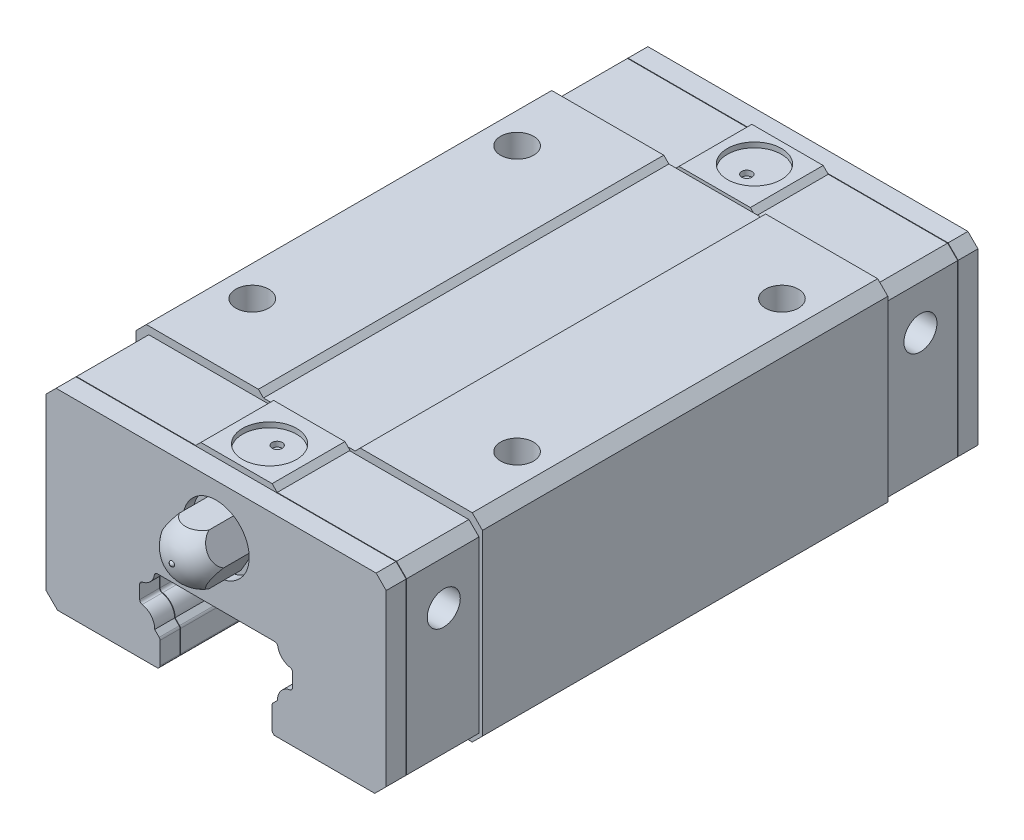
SolidWorks part; units mm, degrees
ref_plane "Front Plane" through (0, 0, 0) normal (0, 0, 1) x (1, 0, 0)
ref_plane "Top Plane" through (0, 0, 0) normal (0, 1, 0) x (1, 0, 0)
ref_plane "Right Plane" through (0, 0, 0) normal (1, 0, 0) x (0, 0, -1)
ref_axis "Axis_X" through (-18.7, 0, 0) along (1, 0, 0)
ref_axis "Axis_Y" through (0, 12.475, 0) along (0, -1, 0)
ref_axis "Axis_Z" through (0, 0, -62.49) along (0, 0, 1)
sketch "Sketch1" plane through (0, 0, 0) normal (0, 0, 1) x (1, 0, 0)
  line L0 (0, 0) -> (0, -12.5) construction
  line L1 (-17, -8) -> (-5.7, -8) construction
  line L2 (-17, -8) -> (-17, 11.5) construction
  line L3 (-17, 11.5) -> (17, 11.5) construction
  line L4 (17, -8) -> (17, 11.5) construction
  line L5 (-17, -8) -> (17, 11.5) construction
  line L6 (-17, 11.5) -> (17, -8) construction
  line L7 (-5.7, -8) -> (-5.5, -7.8)
  line L8 (-5.5, -7.8) -> (-5.5, -5.4)
  line L9 (-5.5, -5.4) -> (-7.5, -5.4)
  line L10 (-7.5, -5.4) -> (-7.5, 0)
  line L11 (7.5, -5.4) -> (7.5, 0)
  line L12 (-7.5, 0) -> (7.5, 0)
  line L13 (5.5, -5.4) -> (7.5, -5.4)
  line L14 (5.5, -7.8) -> (5.5, -5.4)
  line L15 (5.7, -8) -> (5.5, -7.8)
  line L16 (5.7, -8) -> (17, -8) construction
  line L17 (-17, -7) -> (-16, -8)
  line L18 (16, -8) -> (17, -7)
  line L19 (-16, -8) -> (-5.7, -8)
  line L20 (-17, 10.5) -> (-17, -7)
  line L21 (5.7, -8) -> (16, -8)
  line L22 (-16, 11.5) -> (16, 11.5)
  line L23 (-17, 10.5) -> (-16, 11.5)
  line L24 (16, 11.5) -> (17, 10.5)
  line L25 (17, 10.5) -> (17, -7)
  point P0 (0, 1.75)
  dimension "W" = 34
  dimension "HR" = 12.5
  dimension "H" = 24
  dimension "H1" = 4.5
  dimension "MSM_21" = 11.4
  dimension "FIX_1" = 45
  dimension "MSM_1" = 11
  dimension "MSM_4" = 7.1
  dimension "WR" = 15
  dimension "FIX_2" = 45
  dimension "FIX_3" = 1
extrude "Boss-Extrude1" add sketch "Sketch1" against normal blind 58.1
sketch "Sketch2" plane through (0, 0, 0) normal (0, 0, 1) x (1, 0, 0)
  line L0 (0, 0) -> (0, 11.5) construction
  line L1 (-7.5, 0) -> (7.5, 0) construction
  line L2 (16, 11.5) -> (-16, 11.5) construction
  line L3 (-5.5, -5.4) -> (-6.0305, -4.8695)
  line L4 (-5.7, -8) -> (-5.5, -7.8) construction
  line L5 (5.5, -5.4) -> (6.0305, -4.8695)
  line L6 (-7.53, -6.33) -> (-5.5, -6.33)
  line L7 (-5.5, -7.8) -> (-5.5, -5.4) construction
  line L8 (-5.5, -6.33) -> (-5.5, -5.4)
  line L9 (7.53, -6.33) -> (5.5, -6.33)
  line L10 (5.5, -5.4) -> (5.5, -7.8) construction
  line L11 (5.5, -6.33) -> (5.5, -5.4)
  circle A0 centre (-7.53, 0.03) radius 1.5
  arc A1 (6.0305, -4.8695) -> (7.53, -6.33) centre (7.53, -4.83) cw
  arc A2 (-6.0305, -4.8695) -> (-7.53, -6.33) centre (-7.53, -4.83) ccw
  circle A3 centre (7.53, 0.03) radius 1.5
  dimension "MSM_5" = 3
  dimension "MSM_6" = 15.06
  dimension "MSM_7" = 4.86
  dimension "MSM_8" = 7.67
extrude "Boss-Extrude2" add sketch "Sketch2" against normal through all
fillet "Fillet1" radius 0.3 6 edges at (7.5, -3.3303, -29.05) (7.5, -1.4697, -29.05) (-7.5, -3.3303, -29.05) (-7.5, -1.4697, -29.05) (6.0303, 0, -29.05) (-6.0303, 0, -29.05)
fillet "Fillet2" radius 0.3 4 edges at (-5.5, -7.8, -29.05) (5.5, -7.8, -29.05) (5.5, -5.4, -29.05) (-5.5, -5.4, -29.05)
sketch "Sketch3" plane through (0, 0, 0) normal (0, 0, 1) x (1, 0, 0)
  line L4 (15.7101, 10.8) -> (16.7, 9.8101)
  line L7 (-15.7101, 10.8) -> (15.7101, 10.8)
  line L11 (-16, 11.5) -> (-17, 10.5)
  line L12 (-15.7101, 10.8) -> (-16.7, 9.8101)
  line L13 (-17, 10.5) -> (-17, -7)
  line L14 (-16, 11.5) -> (16, 11.5)
  line L15 (16, 11.5) -> (17, 10.5)
  line L16 (-17, -7) -> (-16, -8)
  line L17 (17, 10.5) -> (17, -7)
  line L18 (17, -7) -> (16, -8)
  line L20 (16, -8) -> (17, -7) construction
  line L21 (16.7, -6.8757) -> (15.5757, -8)
  line L22 (16.7, 9.8101) -> (16.7, -6.8757)
  line L23 (-15.7101, 10.8) -> (-16.505, 10.005) construction
  line L24 (15.7101, 10.8) -> (16.505, 10.005) construction
  line L25 (-16.7, -6.8757) -> (-15.7879, -7.7879) construction
  line L26 (-16.7, 9.8101) -> (-16.7, -6.8757)
  line L27 (-16.7, -6.8757) -> (-15.5757, -8)
  line L28 (-15.8757, 11.2) -> (-16.7, 10.3757) construction
  line L29 (-15.8757, 11.2) -> (15.8757, 11.2) construction
  line L30 (15.8757, 11.2) -> (16.7, 10.3757) construction
  line L31 (-16.7, 10.3757) -> (-16.7, -6.8757) construction
  line L32 (16.7, 10.3757) -> (16.7, -6.8757) construction
  line L33 (-16, -8) -> (-5.7, -8) construction
  line L34 (-16, -8) -> (-15.5757, -8)
  line L35 (16.7, -6.8757) -> (15.7879, -7.7879) construction
  line L36 (5.7, -8) -> (16, -8) construction
  line L37 (17, -7) -> (16, -8) construction
  line L38 (15.5757, -8) -> (16, -8)
  point P11 (-16.7, -6.8757)
  point P12 (-16.7, 11.2)
  point P13 (16.7, 11.2)
  point P14 (16.7, -6.8757)
  dimension "KSS_1" = 0.7
  dimension "FIX_5" = 0.3
extrude "Cut-Extrude1" cut sketch "Sketch3" against normal blind 9.15
ref_plane "Plane1" through (0, 0, -48.95) normal (0, 0, 1) x (1, 0, 0)
sketch "Sketch4" plane through (0, 0, -48.95) normal (0, 0, 1) x (1, 0, 0)
  line L8 (-16, -8) -> (-15.5757, -8)
  line L9 (-16, -8) -> (-15.5757, -8)
  line L10 (-16, 11.5) -> (-17, 10.5)
  line L11 (-16, 11.5) -> (-17, 10.5)
  line L12 (-16.7, 9.8101) -> (-15.7101, 10.8)
  line L13 (-16.7, 9.8101) -> (-15.7101, 10.8)
  line L14 (-15.5757, -8) -> (-16.7, -6.8757)
  line L15 (-15.5757, -8) -> (-16.7, -6.8757)
  line L16 (-16.7, -6.8757) -> (-16.7, 9.8101)
  line L17 (-16.7, -6.8757) -> (-16.7, 9.8101)
  line L18 (16, -8) -> (17, -7)
  line L19 (16, -8) -> (17, -7)
  line L20 (17, -7) -> (17, 10.5)
  line L21 (17, -7) -> (17, 10.5)
  line L22 (-17, -7) -> (-16, -8)
  line L23 (-17, -7) -> (-16, -8)
  line L28 (17, 10.5) -> (16, 11.5)
  line L29 (17, 10.5) -> (16, 11.5)
  line L30 (-15.7101, 10.8) -> (15.7101, 10.8)
  line L31 (-15.7101, 10.8) -> (15.7101, 10.8)
  line L32 (-17, 10.5) -> (-17, -7)
  line L33 (-17, 10.5) -> (-17, -7)
  line L34 (16, 11.5) -> (-16, 11.5)
  line L35 (16, 11.5) -> (-16, 11.5)
  line L40 (15.7101, 10.8) -> (16.7, 9.8101)
  line L41 (15.7101, 10.8) -> (16.7, 9.8101)
  line L42 (16.7, 9.8101) -> (16.7, -6.8757)
  line L43 (16.7, 9.8101) -> (16.7, -6.8757)
  line L44 (16.7, -6.8757) -> (15.5757, -8)
  line L45 (16.7, -6.8757) -> (15.5757, -8)
  line L46 (15.5757, -8) -> (16, -8)
  line L47 (15.5757, -8) -> (16, -8)
  dimension "FIX_6" = 0
extrude "Cut-Extrude2" cut sketch "Sketch4" against normal through all
sketch "Sketch5" plane through (0, 0, -9.15) normal (0, 0, 1) x (1, 0, 0)
  line L0 (-4.5, 11) -> (4.5, 11)
  line L1 (0, 0) -> (0, 11) construction
  line L3 (-4.5, 11) -> (-5, 11.5)
  line L4 (4.5, 11) -> (5, 11.5)
  line L5 (-5, 11.5) -> (5, 11.5)
  line L6 (16, 11.5) -> (-16, 11.5) construction
  dimension "MSM_23" = 10
  dimension "FIX_7" = 0.5
  dimension "FIX_8" = 135
extrude "Cut-Extrude3" cut sketch "Sketch5" against normal through all
sketch "Sketch6" plane through (0, 10.8, 0) normal (0, 1, 0) x (1, 0, 0)
  line L0 (0, 0) -> (0, 2) construction
  line L1 (-4, 56.1) -> (4, 56.1)
  line L2 (-4, 56.1) -> (-4, 48.95)
  line L3 (-4, 48.95) -> (4, 48.95)
  line L4 (4, 56.1) -> (4, 48.95)
  line L5 (-4, 9.15) -> (4, 9.15)
  line L6 (-4, 9.15) -> (-4, 2)
  line L7 (-4, 2) -> (4, 2)
  line L8 (4, 9.15) -> (4, 2)
  line L9 (-15.7101, 9.15) -> (15.7101, 9.15) construction
  line L10 (-4.5, 48.95) -> (4.5, 48.95) construction
  dimension "MSM_24" = 7.15
  dimension "MSM_25" = 8
extrude "Boss-Extrude3" add sketch "Sketch6" along normal blind 0.5
chamfer "Chamfer1" distance 0.5 angle 45 4 edges at (4, 11.3, -5.575) (-4, 11.3, -5.575) (4, 11.3, -52.525) (-4, 11.3, -52.525)
sketch "Sketch7" plane through (0, 0, -48.95) normal (0, 0, -1) x (-1, 0, 0)
  line L0 (5, 11.5) -> (16, 11.5) construction
  line L9 (15.5757, -8) -> (16, -8)
  line L10 (16, -8) -> (17, -7)
  line L11 (17, -7) -> (17, 5.5)
  line L12 (17, 10.5) -> (17, -7) construction
  line L15 (16.7, 5.2) -> (16.7, -6.8757)
  line L16 (16.7, -6.8757) -> (15.5757, -8)
  line L18 (17, 5.5) -> (16.7, 5.2)
  dimension "T" = 6
  dimension "FIX_10" = 45
extrude "Cut-Extrude4" cut sketch "Sketch7" against normal through all
sketch "Sketch8" plane through (0, 11.3, 0) normal (0, 1, 0) x (1, 0, 0)
  line L3 (0, 2) -> (0, 56.1) construction
  line L4 (-4, 2) -> (4, 2) construction
  line L5 (4, 56.1) -> (-4, 56.1) construction
  line L6 (-15.7101, 58.1) -> (15.7101, 58.1) construction
  circle A0 centre (0, 52.85) radius 2.65
  circle A1 centre (0, 5.25) radius 2.65
  dimension "KSS_4" = 5.3
extrude "Cut-Extrude5" cut sketch "Sketch8" against normal blind 0.5
sketch "Sketch9" plane through (0, 10.8, 0) normal (0, 1, 0) x (1, 0, 0)
  line L0 (0, 0) -> (0, 56.1) construction
  line L1 (-15.7101, 0) -> (15.7101, 0) construction
  line L2 (4, 56.1) -> (-4, 56.1) construction
  circle A0 centre (0, 6) radius 0.5
  circle A1 centre (0, 52.1) radius 0.5
  circle A2 centre (0, 5.25) radius 2.65 construction
  circle A3 centre (0, 52.85) radius 2.65 construction
  dimension "FIX_11" = 1
extrude "Cut-Extrude6" cut sketch "Sketch9" against normal blind 0.5
sketch "Sketch10" plane through (0, 10.8, 0) normal (0, 1, 0) x (1, 0, 0)
  line L0 (0, 6) -> (0, 5.25) construction
  line L1 (0.5, 6) -> (0.5, 5.25)
  line L2 (-0.5, 6) -> (-0.5, 5.25)
  line L3 (0, 52.85) -> (0, 52.1) construction
  line L4 (0.5, 52.85) -> (0.5, 52.1)
  line L5 (-0.5, 52.85) -> (-0.5, 52.1)
  arc A0 (0.5, 6) -> (-0.5, 6) centre (0, 6) ccw
  arc A1 (-0.5, 5.25) -> (0.5, 5.25) centre (0, 5.25) ccw
  circle A2 centre (0, 6) radius 0.5 construction
  arc A3 (0.5, 52.85) -> (-0.5, 52.85) centre (0, 52.85) ccw
  arc A4 (-0.5, 52.1) -> (0.5, 52.1) centre (0, 52.1) ccw
  circle A6 centre (0, 52.1) radius 0.5 construction
  point P4 (0, 5.625)
  point P15 (0, 52.475)
extrude "Cut-Extrude7" [suppressed] cut sketch "Sketch10" against normal blind 0.3
hole_wizard "Tap1" positions "Sketch12" profile "Sketch11" hole size "M4x0.7" standard "JIS"
sketch "Sketch12" plane through (0, 11.5, 0) normal (0, 1, 0) x (1, 0, 0)
  line L0 (-17, 48.95) -> (-17, 9.15) construction
  circle A0 centre (0, 52.85) radius 2.65 construction
  point P0 (-13, 42.55)
  point P2 (13, 42.55)
  point P4 (13, 16.55)
  point P6 (-13, 16.55)
  dimension "B" = 26
  dimension "C" = 26
  dimension "B1" = 4
  dimension "K1" = 10.3
sketch "Sketch11" plane through (-13, 11.5, -42.55) normal (1, 0, 0) x (0, 0, 1)
  line L0 (0, 0) -> (0, 6.974)
  line L1 (0, 6.974) -> (1.621, 6)
  line L2 (1.621, 6) -> (1.621, 0)
  line L5 (1.621, 0) -> (0, 0)
  line L10 (0, 6.974) -> (-1.621, 6) construction
  line L11 (0, -6.35) -> (0, 107.95) construction
  dimension "HSD_1" = 3.242
  dimension "L_s" = 6
  dimension "Drill Angle" = 118
hole_wizard "Tap2" positions "Sketch14" profile "Sketch13" hole size "M4x0.7" standard "JIS"
sketch "Sketch14" plane through (16.7, 0, 0) normal (1, 0, 0) x (0, 0, -1)
  line L1 (9.15, 9.8101) -> (9.15, -6.8757) construction
  line L2 (48.95, 9.8101) -> (48.95, -6.8757) construction
  point P0 (5.65, 5.5)
  point P2 (52.45, 5.5)
  dimension "H3" = 6
sketch "Sketch13" plane through (16.7, 5.5, -5.65) normal (0, 1, 0) x (0, 0, -1)
  line L0 (0, 0) -> (0, 5.474)
  line L1 (0, 5.474) -> (1.621, 4.5)
  line L2 (1.621, 4.5) -> (1.621, 0)
  line L5 (1.621, 0) -> (0, 0)
  line L10 (0, 5.474) -> (-1.621, 4.5) construction
  line L11 (0, -6.35) -> (0, 107.95) construction
  dimension "HSD_2" = 3.242
  dimension "HSL_2" = 4.5
  dimension "Drill Angle" = 118
hole_wizard "Tap3" positions "Sketch16" profile "Sketch15" hole size "M4x0.7" standard "JIS"
sketch "Sketch16" plane through (-16.7, 0, 0) normal (-1, 0, 0) x (0, 0, 1)
  line L1 (-48.95, 10.5) -> (-48.95, 5.5) construction
  line L3 (-9.15, 10.5) -> (-9.15, 5.5) construction
  point P0 (-52.45, 5.5)
  point P2 (-5.65, 5.5)
  dimension "H3" = 6
sketch "Sketch15" plane through (-16.7, 5.5, -52.45) normal (0, 1, 0) x (0, 0, 1)
  line L0 (0, 0) -> (0, 5.474)
  line L1 (0, 5.474) -> (1.621, 4.5)
  line L2 (1.621, 4.5) -> (1.621, 0)
  line L5 (1.621, 0) -> (0, 0)
  line L10 (0, 5.474) -> (-1.621, 4.5) construction
  line L11 (0, -6.35) -> (0, 107.95) construction
  dimension "HSD_2" = 3.242
  dimension "HSL_2" = 4.5
  dimension "Drill Angle" = 118
sketch "Sketch17" plane through (0, 0, 0) normal (0, 0, 1) x (1, 0, 0)
  line L0 (16, 11.5) -> (5, 11.5) construction
  circle A0 centre (0, 5.9) radius 3.25
  dimension "H2" = 5.6
  dimension "MSM_28" = 6.5
extrude "Cut-Extrude8" cut sketch "Sketch17" against normal blind 1
sketch "Sketch18" plane through (0, 0, -1) normal (0, 0, 1) x (1, 0, 0)
  line L1 (1.4434, 8.4) -> (-1.4434, 8.4)
  line L2 (-1.4434, 8.4) -> (-2.8868, 5.9)
  line L3 (-2.8868, 5.9) -> (-1.4434, 3.4)
  line L4 (-1.4434, 3.4) -> (1.4434, 3.4)
  line L5 (1.4434, 3.4) -> (2.8868, 5.9)
  line L6 (2.8868, 5.9) -> (1.4434, 8.4)
  circle A0 centre (0, 5.9) radius 2.5 construction
  dimension "FIX_15" = 5
extrude "Boss-Extrude4" add sketch "Sketch18" along normal blind 5.34
sketch "Sketch19" plane through (0, 0, 0) normal (1, 0, 0) x (0, 0, -1)
  line L0 (0, 5.9) -> (-4.34, 5.9) construction
  line L1 (-4.34, 5.9) -> (1, 5.9) construction
  line L2 (0, 9.8101) -> (0, -6.8757) construction
  line L3 (-4.34, 5.9) -> (-4.34, 8.4) construction
  line L4 (-4.44, 8.9) -> (-4.44, 5.9)
  line L5 (-4.44, 8.9) -> (-1.34, 8.9)
  line L6 (-4.44, 5.9) -> (-4.34, 5.9)
  arc A0 (-1.34, 8.9) -> (-4.34, 5.9) centre (-1.34, 5.9) ccw
  dimension "FIX_17" = 6
  dimension "FIX_18" = 0.1
revolve "Cut-Revolve1" cut sketch "Sketch19" angle 360 about L0
sketch "Sketch20" plane through (0, 0, 0) normal (1, 0, 0) x (0, 0, -1)
  line L0 (0, 5.9) -> (-4.22, 5.9) construction
  line L1 (-2.1565, 5.9) -> (1, 5.9) construction
  line L2 (0, 9.8101) -> (0, -6.8757) construction
  line L3 (-3.94, 5.9) -> (-4.5, 5.9)
  arc A0 (-3.94, 5.9) -> (-4.5, 5.9) centre (-4.22, 5.9) ccw
  dimension "FIX_20" = 0.56
  dimension "FIX_101" = 4.5
revolve "Revolve1" add sketch "Sketch20" angle 360 about L0
sketch "Sketch21" plane through (0, 0, -58.1) normal (0, 0, -1) x (-1, 0, 0)
  line L0 (-16, 11.5) -> (-5, 11.5) construction
  circle A2 centre (0, 5.9) radius 3.25
  dimension "H2" = 5.6
  dimension "MSM_28" = 6.5
extrude "Cut-Extrude9" cut sketch "Sketch21" against normal blind 1
sketch "Sketch22" plane through (0, 0, -57.1) normal (0, 0, -1) x (-1, 0, 0)
  circle A0 centre (0, 5.9) radius 2.75
  dimension "KSS_7" = 5.5
extrude "Boss-Extrude5" add sketch "Sketch22" along normal blind 2.2
sketch "Sketch23" plane through (0, 0, -59.3) normal (0, 0, -1) x (-1, 0, 0)
  line L1 (0.7217, 7.15) -> (-0.7217, 7.15)
  line L2 (-0.7217, 7.15) -> (-1.4434, 5.9)
  line L3 (-1.4434, 5.9) -> (-0.7217, 4.65)
  line L4 (-0.7217, 4.65) -> (0.7217, 4.65)
  line L5 (0.7217, 4.65) -> (1.4434, 5.9)
  line L6 (1.4434, 5.9) -> (0.7217, 7.15)
  circle A0 centre (0, 5.9) radius 1.25 construction
  dimension "KSS_8" = 2.5
extrude "Cut-Extrude10" cut sketch "Sketch23" against normal blind 1.4
fillet "Fillet3" radius 1.3 1 edges at (-2.75, 5.9, -59.3)
ref_plane "Plane2" through (0, 0, -2) normal (0, 0, 1) x (1, 0, 0)
sketch "Sketch24" plane through (0, 0, -2) normal (0, 0, 1) x (1, 0, 0)
  line L76 (15.555, -7.95) -> (16.65, -6.855)
  line L77 (16.65, -6.855) -> (16.65, 9.7893)
  line L78 (16.65, 9.7893) -> (15.6893, 10.75)
  line L99 (15.6893, 10.75) -> (-15.6893, 10.75)
  line L100 (-15.6893, 10.75) -> (-16.65, 9.7893)
  line L101 (-16.65, 9.7893) -> (-16.65, -6.855)
  line L102 (-16.65, -6.855) -> (-15.555, -7.95)
  line L103 (-15.555, -7.95) -> (-5.7207, -7.95)
  line L104 (-5.7207, -7.95) -> (-5.6232, -7.8525)
  line L105 (-5.55, -7.6757) -> (-5.55, -5.5243)
  line L106 (-5.6232, -5.3475) -> (-6.0812, -4.8895)
  line L107 (-7.55, -3.0605) -> (-7.55, -1.7395)
  line L108 (-5.7605, 0.05) -> (5.7605, 0.05)
  line L109 (7.55, -1.7395) -> (7.55, -3.0605)
  line L110 (6.0812, -4.8895) -> (5.6232, -5.3475)
  line L111 (5.55, -5.5243) -> (5.55, -7.6757)
  line L112 (5.6232, -7.8525) -> (5.7207, -7.95)
  line L113 (5.7207, -7.95) -> (15.555, -7.95)
  line L114 (15.5757, -8) -> (16.7, -6.8757)
  line L115 (16.7, -6.8757) -> (16.7, 9.8101)
  line L136 (16.7, 9.8101) -> (15.7101, 10.8)
  line L137 (15.7101, 10.8) -> (-15.7101, 10.8)
  line L138 (-15.7101, 10.8) -> (-16.7, 9.8101)
  line L139 (-16.7, 9.8101) -> (-16.7, -6.8757)
  line L140 (-16.7, -6.8757) -> (-15.5757, -8)
  line L141 (-15.5757, -8) -> (-5.7, -8)
  line L142 (-5.7, -8) -> (-5.5879, -7.8879)
  line L143 (-5.5, -7.6757) -> (-5.5, -5.5243)
  line L144 (-5.5879, -5.3121) -> (-6.0305, -4.8695)
  line L145 (-7.5, -3.0605) -> (-7.5, -1.7395)
  line L146 (-5.7605, 0) -> (5.7605, 0)
  line L147 (7.5, -1.7395) -> (7.5, -3.0605)
  line L148 (6.0305, -4.8695) -> (5.5879, -5.3121)
  line L149 (5.5, -5.5243) -> (5.5, -7.6757)
  line L150 (5.5879, -7.8879) -> (5.7, -8)
  line L151 (5.7, -8) -> (15.5757, -8)
  line L152 (15.5757, -8) -> (16.7, -6.8757)
  line L153 (16.7, -6.8757) -> (16.7, 9.8101)
  line L154 (16.7, 9.8101) -> (15.7101, 10.8)
  line L155 (15.7101, 10.8) -> (-15.7101, 10.8)
  line L156 (-15.7101, 10.8) -> (-16.7, 9.8101)
  line L157 (-16.7, 9.8101) -> (-16.7, -6.8757)
  line L158 (-16.7, -6.8757) -> (-15.5757, -8)
  line L159 (-15.5757, -8) -> (-5.7, -8)
  line L160 (-5.7, -8) -> (-5.5879, -7.8879)
  line L161 (-5.5, -7.6757) -> (-5.5, -5.5243)
  line L162 (-5.5879, -5.3121) -> (-6.0305, -4.8695)
  line L163 (-7.5, -3.0605) -> (-7.5, -1.7395)
  line L164 (-5.7605, 0) -> (5.7605, 0)
  line L165 (7.5, -1.7395) -> (7.5, -3.0605)
  line L166 (6.0305, -4.8695) -> (5.5879, -5.3121)
  line L167 (5.5, -5.5243) -> (5.5, -7.6757)
  line L168 (5.5879, -7.8879) -> (5.7, -8)
  line L169 (5.7, -8) -> (15.5757, -8)
  arc A60 (-5.6232, -7.8525) -> (-5.55, -7.6757) centre (-5.8, -7.6757) ccw
  arc A61 (-5.55, -5.5243) -> (-5.6232, -5.3475) centre (-5.8, -5.5243) ccw
  arc A62 (-6.0812, -4.8895) -> (-7.2642, -3.4046) centre (-7.53, -4.83) ccw
  arc A63 (-7.55, -3.0605) -> (-7.2642, -3.4046) centre (-7.2, -3.0605) ccw
  arc A64 (-7.2642, -1.3954) -> (-7.55, -1.7395) centre (-7.2, -1.7395) ccw
  arc A65 (-7.2642, -1.3954) -> (-6.1046, -0.2358) centre (-7.53, 0.03) ccw
  arc A66 (-5.7605, 0.05) -> (-6.1046, -0.2358) centre (-5.7605, -0.3) ccw
  arc A67 (6.1046, -0.2358) -> (5.7605, 0.05) centre (5.7605, -0.3) ccw
  arc A68 (6.1046, -0.2358) -> (7.2642, -1.3954) centre (7.53, 0.03) ccw
  arc A69 (7.55, -1.7395) -> (7.2642, -1.3954) centre (7.2, -1.7395) ccw
  arc A70 (7.2642, -3.4046) -> (7.55, -3.0605) centre (7.2, -3.0605) ccw
  arc A71 (7.2642, -3.4046) -> (6.0812, -4.8895) centre (7.53, -4.83) ccw
  arc A84 (5.6232, -5.3475) -> (5.55, -5.5243) centre (5.8, -5.5243) ccw
  arc A85 (5.55, -7.6757) -> (5.6232, -7.8525) centre (5.8, -7.6757) ccw
  arc A86 (-5.5879, -7.8879) -> (-5.5, -7.6757) centre (-5.8, -7.6757) ccw
  arc A87 (-5.5, -5.5243) -> (-5.5879, -5.3121) centre (-5.8, -5.5243) ccw
  arc A88 (-6.0305, -4.8695) -> (-7.255, -3.3554) centre (-7.53, -4.83) ccw
  arc A89 (-7.5, -3.0605) -> (-7.255, -3.3554) centre (-7.2, -3.0605) ccw
  arc A90 (-7.255, -1.4446) -> (-7.5, -1.7395) centre (-7.2, -1.7395) ccw
  arc A91 (-7.255, -1.4446) -> (-6.0554, -0.245) centre (-7.53, 0.03) ccw
  arc A92 (-5.7605, 0) -> (-6.0554, -0.245) centre (-5.7605, -0.3) ccw
  arc A93 (6.0554, -0.245) -> (5.7605, 0) centre (5.7605, -0.3) ccw
  arc A94 (6.0554, -0.245) -> (7.255, -1.4446) centre (7.53, 0.03) ccw
  arc A95 (7.5, -1.7395) -> (7.255, -1.4446) centre (7.2, -1.7395) ccw
  arc A96 (7.255, -3.3554) -> (7.5, -3.0605) centre (7.2, -3.0605) ccw
  arc A97 (7.255, -3.3554) -> (6.0305, -4.8695) centre (7.53, -4.83) ccw
  arc A98 (5.5879, -5.3121) -> (5.5, -5.5243) centre (5.8, -5.5243) ccw
  arc A99 (5.5, -7.6757) -> (5.5879, -7.8879) centre (5.8, -7.6757) ccw
  arc A100 (-5.5879, -7.8879) -> (-5.5, -7.6757) centre (-5.8, -7.6757) ccw
  arc A101 (-5.5, -5.5243) -> (-5.5879, -5.3121) centre (-5.8, -5.5243) ccw
  arc A102 (-6.0305, -4.8695) -> (-7.255, -3.3554) centre (-7.53, -4.83) ccw
  arc A103 (-7.5, -3.0605) -> (-7.255, -3.3554) centre (-7.2, -3.0605) ccw
  arc A104 (-7.255, -1.4446) -> (-7.5, -1.7395) centre (-7.2, -1.7395) ccw
  arc A105 (-7.255, -1.4446) -> (-6.0554, -0.245) centre (-7.53, 0.03) ccw
  arc A106 (-5.7605, 0) -> (-6.0554, -0.245) centre (-5.7605, -0.3) ccw
  arc A107 (6.0554, -0.245) -> (5.7605, 0) centre (5.7605, -0.3) ccw
  arc A108 (6.0554, -0.245) -> (7.255, -1.4446) centre (7.53, 0.03) ccw
  arc A109 (7.5, -1.7395) -> (7.255, -1.4446) centre (7.2, -1.7395) ccw
  arc A110 (7.255, -3.3554) -> (7.5, -3.0605) centre (7.2, -3.0605) ccw
  arc A111 (7.255, -3.3554) -> (6.0305, -4.8695) centre (7.53, -4.83) ccw
  arc A112 (5.5879, -5.3121) -> (5.5, -5.5243) centre (5.8, -5.5243) ccw
  arc A113 (5.5, -7.6757) -> (5.5879, -7.8879) centre (5.8, -7.6757) ccw
  dimension "FIX_25" = 0.05
  dimension "D1" = 0
extrude "Cut-Extrude11" cut sketch "Sketch24" along normal blind 0.05
ref_plane "Plane3" through (0, 0, -9.15) normal (0, 0, 1) x (1, 0, 0)
sketch "Sketch25" plane through (0, 0, -9.15) normal (0, 0, 1) x (1, 0, 0)
  line L0 (15.555, -7.95) -> (16.65, -6.855)
  line L1 (16.65, -6.855) -> (16.65, 9.7893)
  line L2 (16.65, 9.7893) -> (15.6893, 10.75)
  line L3 (15.6893, 10.75) -> (-15.6893, 10.75)
  line L4 (-15.6893, 10.75) -> (-16.65, 9.7893)
  line L5 (-16.65, 9.7893) -> (-16.65, -6.855)
  line L6 (-16.65, -6.855) -> (-15.555, -7.95)
  line L7 (-15.555, -7.95) -> (-5.7207, -7.95)
  line L8 (-5.7207, -7.95) -> (-5.6232, -7.8525)
  line L9 (-5.55, -7.6757) -> (-5.55, -5.5243)
  line L10 (-5.6232, -5.3475) -> (-6.0812, -4.8895)
  line L11 (-7.55, -3.0605) -> (-7.55, -1.7395)
  line L12 (-5.7605, 0.05) -> (5.7605, 0.05)
  line L13 (7.55, -1.7395) -> (7.55, -3.0605)
  line L14 (6.0812, -4.8895) -> (5.6232, -5.3475)
  line L15 (5.55, -5.5243) -> (5.55, -7.6757)
  line L16 (5.6232, -7.8525) -> (5.7207, -7.95)
  line L17 (5.7207, -7.95) -> (15.555, -7.95)
  line L18 (15.5757, -8) -> (16.7, -6.8757)
  line L19 (16.7, -6.8757) -> (16.7, 9.8101)
  line L20 (16.7, 9.8101) -> (15.7101, 10.8)
  line L21 (15.7101, 10.8) -> (-15.7101, 10.8)
  line L22 (-15.7101, 10.8) -> (-16.7, 9.8101)
  line L23 (-16.7, 9.8101) -> (-16.7, -6.8757)
  line L24 (-16.7, -6.8757) -> (-15.5757, -8)
  line L25 (-15.5757, -8) -> (-5.7, -8)
  line L26 (-5.7, -8) -> (-5.5879, -7.8879)
  line L27 (-5.5, -7.6757) -> (-5.5, -5.5243)
  line L28 (-5.5879, -5.3121) -> (-6.0305, -4.8695)
  line L29 (-7.5, -3.0605) -> (-7.5, -1.7395)
  line L30 (-5.7605, 0) -> (5.7605, 0)
  line L31 (7.5, -1.7395) -> (7.5, -3.0605)
  line L32 (6.0305, -4.8695) -> (5.5879, -5.3121)
  line L33 (5.5, -5.5243) -> (5.5, -7.6757)
  line L34 (5.5879, -7.8879) -> (5.7, -8)
  line L35 (5.7, -8) -> (15.5757, -8)
  line L36 (15.5757, -8) -> (16.7, -6.8757)
  line L37 (16.7, -6.8757) -> (16.7, 9.8101)
  line L38 (16.7, 9.8101) -> (15.7101, 10.8)
  line L39 (15.7101, 10.8) -> (-15.7101, 10.8)
  line L40 (-15.7101, 10.8) -> (-16.7, 9.8101)
  line L41 (-16.7, 9.8101) -> (-16.7, -6.8757)
  line L42 (-16.7, -6.8757) -> (-15.5757, -8)
  line L43 (-15.5757, -8) -> (-5.7, -8)
  line L44 (-5.7, -8) -> (-5.5879, -7.8879)
  line L45 (-5.5, -7.6757) -> (-5.5, -5.5243)
  line L46 (-5.5879, -5.3121) -> (-6.0305, -4.8695)
  line L47 (-7.5, -3.0605) -> (-7.5, -1.7395)
  line L48 (-5.7605, 0) -> (5.7605, 0)
  line L49 (7.5, -1.7395) -> (7.5, -3.0605)
  line L50 (6.0305, -4.8695) -> (5.5879, -5.3121)
  line L51 (5.5, -5.5243) -> (5.5, -7.6757)
  line L52 (5.5879, -7.8879) -> (5.7, -8)
  line L53 (5.7, -8) -> (15.5757, -8)
  arc A0 (-5.6232, -7.8525) -> (-5.55, -7.6757) centre (-5.8, -7.6757) ccw
  arc A1 (-5.55, -5.5243) -> (-5.6232, -5.3475) centre (-5.8, -5.5243) ccw
  arc A2 (-6.0812, -4.8895) -> (-7.2642, -3.4046) centre (-7.53, -4.83) ccw
  arc A3 (-7.55, -3.0605) -> (-7.2642, -3.4046) centre (-7.2, -3.0605) ccw
  arc A4 (-7.2642, -1.3954) -> (-7.55, -1.7395) centre (-7.2, -1.7395) ccw
  arc A5 (-7.2642, -1.3954) -> (-6.1046, -0.2358) centre (-7.53, 0.03) ccw
  arc A6 (-5.7605, 0.05) -> (-6.1046, -0.2358) centre (-5.7605, -0.3) ccw
  arc A7 (6.1046, -0.2358) -> (5.7605, 0.05) centre (5.7605, -0.3) ccw
  arc A8 (6.1046, -0.2358) -> (7.2642, -1.3954) centre (7.53, 0.03) ccw
  arc A9 (7.55, -1.7395) -> (7.2642, -1.3954) centre (7.2, -1.7395) ccw
  arc A10 (7.2642, -3.4046) -> (7.55, -3.0605) centre (7.2, -3.0605) ccw
  arc A11 (7.2642, -3.4046) -> (6.0812, -4.8895) centre (7.53, -4.83) ccw
  arc A12 (5.6232, -5.3475) -> (5.55, -5.5243) centre (5.8, -5.5243) ccw
  arc A13 (5.55, -7.6757) -> (5.6232, -7.8525) centre (5.8, -7.6757) ccw
  arc A14 (-5.5879, -7.8879) -> (-5.5, -7.6757) centre (-5.8, -7.6757) ccw
  arc A15 (-5.5, -5.5243) -> (-5.5879, -5.3121) centre (-5.8, -5.5243) ccw
  arc A16 (-6.0305, -4.8695) -> (-7.255, -3.3554) centre (-7.53, -4.83) ccw
  arc A17 (-7.5, -3.0605) -> (-7.255, -3.3554) centre (-7.2, -3.0605) ccw
  arc A18 (-7.255, -1.4446) -> (-7.5, -1.7395) centre (-7.2, -1.7395) ccw
  arc A19 (-7.255, -1.4446) -> (-6.0554, -0.245) centre (-7.53, 0.03) ccw
  arc A20 (-5.7605, 0) -> (-6.0554, -0.245) centre (-5.7605, -0.3) ccw
  arc A21 (6.0554, -0.245) -> (5.7605, 0) centre (5.7605, -0.3) ccw
  arc A22 (6.0554, -0.245) -> (7.255, -1.4446) centre (7.53, 0.03) ccw
  arc A23 (7.5, -1.7395) -> (7.255, -1.4446) centre (7.2, -1.7395) ccw
  arc A24 (7.255, -3.3554) -> (7.5, -3.0605) centre (7.2, -3.0605) ccw
  arc A25 (7.255, -3.3554) -> (6.0305, -4.8695) centre (7.53, -4.83) ccw
  arc A26 (5.5879, -5.3121) -> (5.5, -5.5243) centre (5.8, -5.5243) ccw
  arc A27 (5.5, -7.6757) -> (5.5879, -7.8879) centre (5.8, -7.6757) ccw
  arc A28 (-5.5879, -7.8879) -> (-5.5, -7.6757) centre (-5.8, -7.6757) ccw
  arc A29 (-5.5, -5.5243) -> (-5.5879, -5.3121) centre (-5.8, -5.5243) ccw
  arc A30 (-6.0305, -4.8695) -> (-7.255, -3.3554) centre (-7.53, -4.83) ccw
  arc A31 (-7.5, -3.0605) -> (-7.255, -3.3554) centre (-7.2, -3.0605) ccw
  arc A32 (-7.255, -1.4446) -> (-7.5, -1.7395) centre (-7.2, -1.7395) ccw
  arc A33 (-7.255, -1.4446) -> (-6.0554, -0.245) centre (-7.53, 0.03) ccw
  arc A34 (-5.7605, 0) -> (-6.0554, -0.245) centre (-5.7605, -0.3) ccw
  arc A35 (6.0554, -0.245) -> (5.7605, 0) centre (5.7605, -0.3) ccw
  arc A36 (6.0554, -0.245) -> (7.255, -1.4446) centre (7.53, 0.03) ccw
  arc A37 (7.5, -1.7395) -> (7.255, -1.4446) centre (7.2, -1.7395) ccw
  arc A38 (7.255, -3.3554) -> (7.5, -3.0605) centre (7.2, -3.0605) ccw
  arc A39 (7.255, -3.3554) -> (6.0305, -4.8695) centre (7.53, -4.83) ccw
  arc A40 (5.5879, -5.3121) -> (5.5, -5.5243) centre (5.8, -5.5243) ccw
  arc A41 (5.5, -7.6757) -> (5.5879, -7.8879) centre (5.8, -7.6757) ccw
  dimension "FIX_27" = 0.05
  dimension "D1" = 0
extrude "Cut-Extrude12" cut sketch "Sketch25" along normal blind 0.05
ref_plane "Plane4" through (0, 0, -29.05) normal (0, 0, 1) x (1, 0, 0)
mirror "Mirror1" about plane through (0, 0, -29.05) normal (0, 0, 1) of "Cut-Extrude12", "Cut-Extrude11"
sketch "Sketch26" plane through (0, 0, 0) normal (0, 0, 1) x (1, 0, 0)
  line L0 (-3.25, 10.8) -> (-3.25, 5.9)
  line L1 (-15.7101, 10.8) -> (15.7101, 10.8) construction
  line L2 (3.25, 10.8) -> (3.25, 5.9)
  line L3 (16, 11.5) -> (5, 11.5) construction
  line L4 (-3.25, 10.8) -> (3.25, 10.8)
  arc A2 (-3.25, 5.9) -> (3.25, 5.9) centre (0, 5.9) ccw
  dimension "H2" = 5.6
  dimension "MSM_28" = 6.5
extrude "Cut-Extrude13" [suppressed] cut sketch "Sketch26" against normal blind 1
sketch "Sketch27" plane through (0, 0, 0) normal (0, 0, 1) x (1, 0, 0)
  line L0 (-10.5, -8) -> (10.5, -8)
  line L1 (-15.5757, -8) -> (-5.7, -8) construction
  line L2 (5.7, -8) -> (15.5757, -8) construction
  line L3 (10.5, -8) -> (0, 2.5)
  line L4 (0, 2.5) -> (-10.5, -8)
  line L5 (0, 0) -> (0, -8) construction
  line L6 (-5.7605, 0) -> (5.7605, 0) construction
  dimension "FIX_99" = 21
extrude "Cut-Extrude14" [suppressed] cut sketch "Sketch27" against normal through all
equation "\"Factor\"= 1.082532"
equation "\"KSS_1@Sketch3\"= if ( \"WR@Sketch1\" = 15 , 0.7 , 1 )"
equation "\"KSS_2@Boss-Extrude3\"= if ( \"WR@Sketch1\" = 15 , 0.5 , 0.8 )"
equation "\"KSS_3@Chamfer1\"= \"KSS_2@Boss-Extrude3\""
equation "\"KSS_4@Sketch8\"= if ( \"WR@Sketch1\" = 15 , 5.3 , 7.3 )"
equation "\"KSS_5@Cut-Extrude5\"= \"KSS_3@Chamfer1\""
equation "\"KSS_6@Boss-Extrude5\"= if ( \"WR@Sketch1\" = 15 , 2.2 , 3 )"
equation "\"KSS_7@Sketch22\"= if ( \"WR@Sketch1\" = 15 , 5.5 , 8 )"
equation "\"KSS_8@Sketch23\"= if ( \"WR@Sketch1\" = 15 , 2.5 , 4 )"
equation "\"KSS_9@Cut-Extrude10\"= if ( \"WR@Sketch1\" = 15 , 1.4 , 2.4 )"
equation "\"KSS_10@Fillet3\"= if ( \"WR@Sketch1\" = 15 , 1.3 , 2.3 )"
